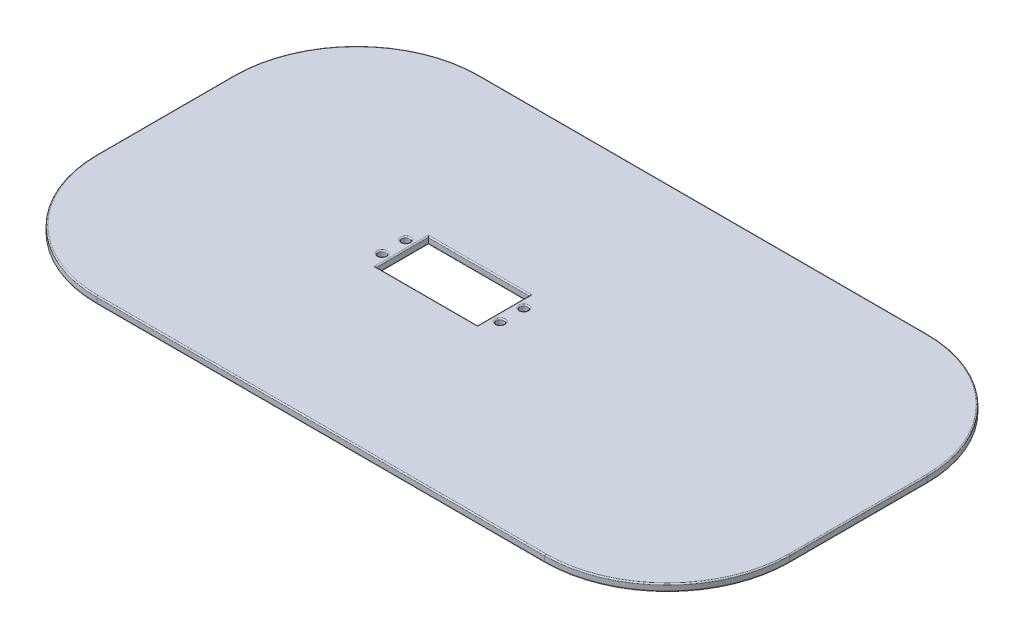
SolidWorks part; units mm, degrees
ref_plane "前视基准面" through (0, 0, 0) normal (0, 0, 1) x (1, 0, 0)
ref_plane "上视基准面" through (0, 0, 0) normal (0, 1, 0) x (1, 0, 0)
ref_plane "右视基准面" through (0, 0, 0) normal (1, 0, 0) x (0, 0, -1)
ref_plane "基准面1" through (0, 1.5, 0) normal (0, 1, 0) x (1, 0, 0)
sketch "草图1" plane through (0, 1.5, 0) normal (0, 1, 0) x (1, 0, 0)
  line L1 (-127.054, -78.7451) -> (158.304, -78.7451)
  line L2 (-127.054, -78.7451) -> (-127.054, 78.7451)
  line L3 (-127.054, 78.7451) -> (158.304, 78.7451)
  line L4 (158.304, -78.7451) -> (158.304, 78.7451)
  line L5 (-127.054, -78.7451) -> (158.304, 78.7451) construction
  line L6 (-127.054, 78.7451) -> (158.304, -78.7451) construction
  line L78 (12.2, -10.75) -> (-29.55, -10.75)
  line L79 (-29.55, -10.75) -> (-29.55, 10.75)
  line L80 (-29.55, 10.75) -> (12.2, 10.75)
  line L81 (12.2, 10.75) -> (12.2, -10.75)
  circle A24 centre (-32.975, 4.875) radius 1.575
  circle A25 centre (-32.975, -4.875) radius 1.575
  circle A26 centre (15.625, -4.875) radius 1.575
  circle A27 centre (15.625, 4.875) radius 1.575
  point P0 (15.625, 0)
extrude "凸台-拉伸1" add sketch "草图1" against normal blind 3
fillet "圆角1" radius 0.5 24 edges at (15.625, -1.5, -78.7451) (-127.054, -1.5, 0) (15.625, -1.5, 78.7451) (158.304, -1.5, 0) (-8.675, -1.5, 10.75) (-29.55, -1.5, 0) (-8.675, -1.5, -10.75) (12.2, -1.5, 0) (-32.975, -1.5, -6.45) (-32.975, -1.5, 3.3) (15.625, -1.5, 3.3) (15.625, -1.5, -6.45) (15.625, 1.5, 78.7451) (-127.054, 1.5, 0) (15.625, 1.5, -78.7451) (158.304, 1.5, 0) (-29.55, 1.5, 0) (-8.675, 1.5, 10.75) (12.2, 1.5, 0) (-8.675, 1.5, -10.75) (-32.975, 1.5, -6.45) (-32.975, 1.5, 3.3) (15.625, 1.5, 3.3) (15.625, 1.5, -6.45)
fillet "圆角2" radius 50.5 12 edges at (-126.9076, 1.3536, 78.5987) (-126.9076, -1.3536, 78.5987) (158.1576, 1.3536, 78.5987) (158.1576, -1.3536, 78.5987) (158.1576, 1.3536, -78.5987) (158.1576, -1.3536, -78.5987) (-126.9076, 1.3536, -78.5987) (-126.9076, -1.3536, -78.5987) (-127.054, 0, -78.7451) (158.304, 0, -78.7451) (158.304, 0, 78.7451) (-127.054, 0, 78.7451)
